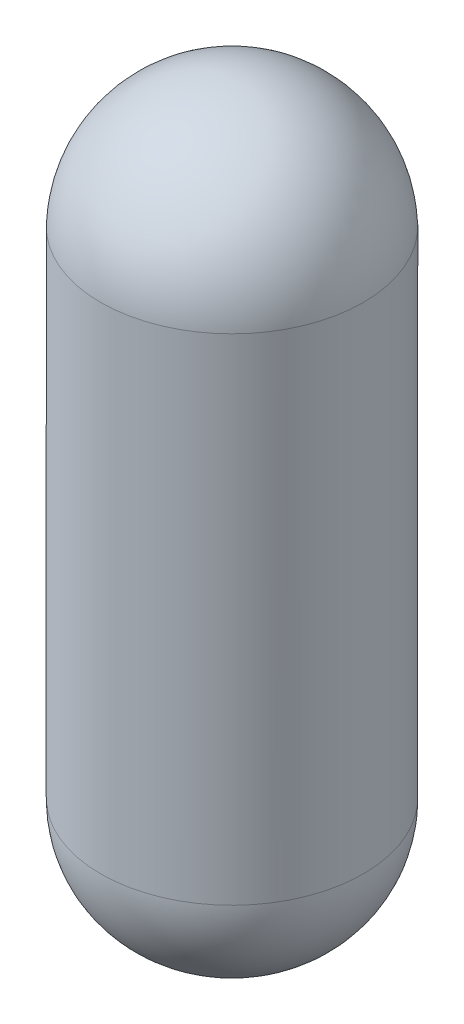
SolidWorks part; units mm, degrees
ref_plane "Front Plane" through (0, 0, 0) normal (0, 0, 1) x (1, 0, 0)
ref_plane "Top Plane" through (0, 0, 0) normal (0, 1, 0) x (1, 0, 0)
ref_plane "Right Plane" through (0, 0, 0) normal (1, 0, 0) x (0, 0, -1)
sketch "Sketch1" plane through (0, 0, 0) normal (0, 0, 1) x (1, 0, 0)
  line L0 (0, 761.7335) -> (0, -1270.2665)
  line L4 (520.7, 715.646) -> (520.7, -1246.0452)
  line L5 (0, 761.7335) -> (0, 1218.9335)
  line L6 (0, -1270.2665) -> (0, -1727.4665)
  arc A3 (0, 1218.9335) -> (520.7, 715.646) centre (0, 697.9323) cw
  arc A4 (520.7, -1246.0452) -> (0, -1727.4665) centre (37.7972, -1246.0452) cw
  point P0 (0, 0)
  point P10 (0, -254.2665)
  dimension "D1" = 520.7
  dimension "D2" = 2032
  dimension "D3" = 1016
  dimension "D4" = 457.2
  dimension "D5" = 457.2
ref_axis "Axis1" through (0, 550, 0) along (0, -1, 0)
revolve "Revolve2" add sketch "Sketch1" angle 360 about axis through (0, 550, 0) along (0, -1, 0)
ref_plane "Plane1" through (0, -254.2665, 0) normal (0, 1, 0) x (1, 0, 0)
